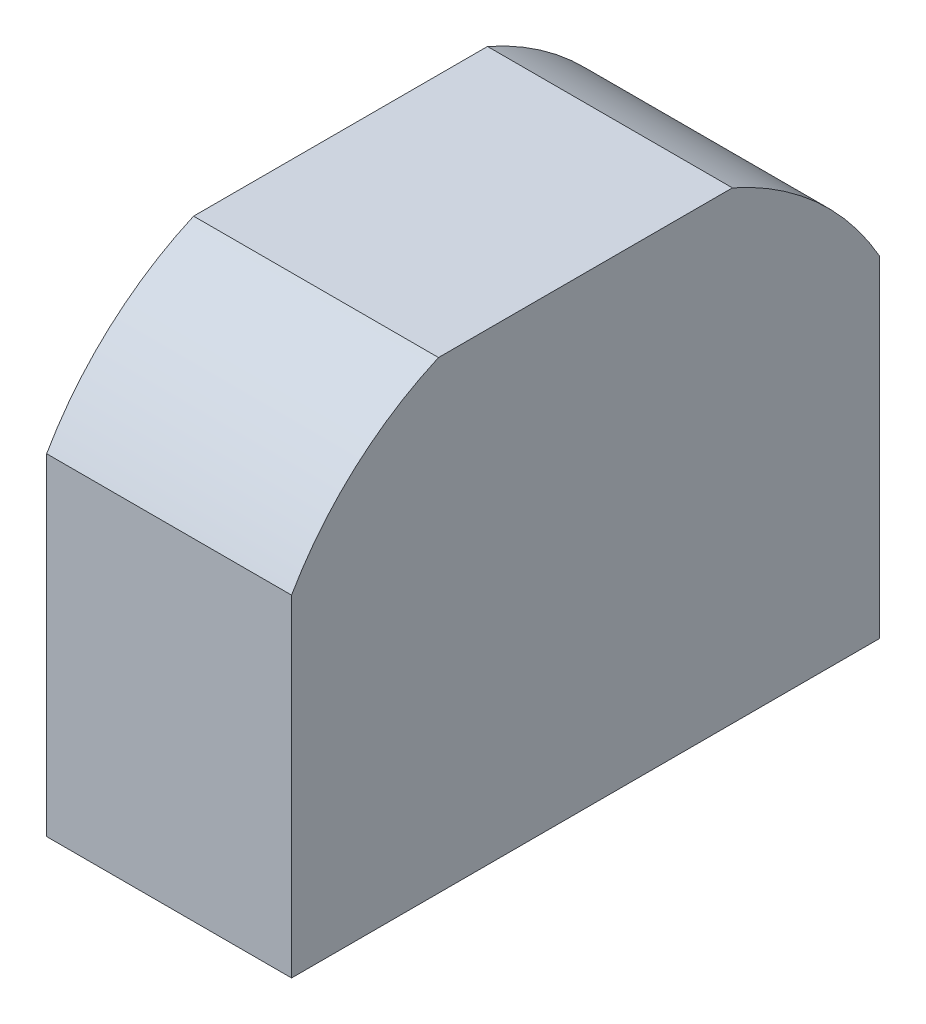
SolidWorks part; units mm, degrees
ref_plane "Front Plane" through (0, 0, 0) normal (0, 0, 1) x (1, 0, 0)
ref_plane "Top Plane" through (0, 0, 0) normal (0, 1, 0) x (1, 0, 0)
ref_plane "Right Plane" through (0, 0, 0) normal (1, 0, 0) x (0, 0, -1)
sketch "Sketch1" plane through (0, 0, 0) normal (0, 0, 1) x (1, 0, 0)
  line L0 (-77.5, 0) -> (77.5, 0)
  arc A0 (77.5, 0) -> (-77.5, 0) centre (0, 0) ccw
  dimension "D1" = 155
extrude "Boss-Extrude1" add sketch "Sketch1" along normal blind 15 and the other way blind 15
sketch "Sketch2" plane through (0, 0, 0) normal (0, -1, 0) x (1, 0, 0)
  line L0 (77.5, -15) -> (77.5, 15) construction
  line L2 (-77.5, 15) -> (77.5, 15) construction
  line L3 (-77.5, -15) -> (77.5, -15) construction
  line L4 (0, 0) -> (0, -15) construction
  circle A0 centre (67.5, 10) radius 2.45
  circle A1 centre (67.5, -10) radius 2.45
  circle A2 centre (-67.5, -10) radius 2.45
  circle A3 centre (-67.5, 10) radius 2.45
  dimension "D1" = 4.9
  dimension "D2" = 10
  dimension "D3" = 2
  dimension "D4" = 20
  dimension "D5" = 5
extrude "Boss-Extrude2" add sketch "Sketch2" along normal blind 5
sketch "Sketch3" plane through (0, 0, 15) normal (0, 0, 1) x (1, 0, 0)
  line L0 (-77.5, 0) -> (77.5, 0) construction
  line L1 (-53.9096, 20) -> (53.9096, 20)
  arc A0 (-53.9096, 20) -> (53.9096, 20) centre (0, 0) ccw
  arc A1 (77.5, 0) -> (-77.5, 0) centre (0, 0) ccw construction
  dimension "D1" = 20
  dimension "D2" = 20
extrude "Cut-Extrude1" cut sketch "Sketch3" against normal through all
ref_plane "Plane1" through (-77.5, 0, 0) normal (1, 0, 0) x (0, 0, -1)
sketch "Sketch4" plane through (-77.5, 0, 0) normal (1, 0, 0) x (0, 0, -1)
  line L0 (0, 0) -> (0, 50)
  line L1 (-30, 0) -> (30, 0)
  line L2 (30, 0) -> (30, 33.8467)
  line L3 (-30, 0) -> (-30, 33.8467)
  arc A0 (30, 33.8467) -> (0, 50) centre (2.0603, 17.8917) ccw
  arc A1 (-30, 33.8467) -> (0, 50) centre (-2.0603, 17.8917) cw
  dimension "D1" = 30
  dimension "D2" = 50
extrude "Boss-Extrude3" add sketch "Sketch4" along normal blind 25 contours L2 A0 L0 L1 | A1 L3 L1 L0 region at (-77.5, 23.0652, 14.1925) region at (-77.5, 23.0652, -14.1925)
sketch "Sketch5" plane through (-77.5, 0, 0) normal (-1, 0, 0) x (0, 0, 1)
  line L0 (0, 50) -> (0, 0) construction
  line L1 (-30, 0) -> (30, 0) construction
  line L2 (6.0867, 27.5001) -> (19.3685, 32.2732)
  line L3 (19.3685, 32.2732) -> (19.3685, 20.2366)
  line L4 (19.3685, 20.2366) -> (6.0867, 20.2366)
  line L5 (6.0867, 20.2366) -> (6.0867, 27.5001)
  line L6 (-12.8314, 8.3557) -> (-12.8314, 6.2286)
  line L7 (-2.6625, 11.728) -> (2.6625, 11.728)
  line L8 (0, 11.728) -> (0, 6.2286)
  line L9 (-2.6625, 6.2286) -> (2.6625, 6.2286)
  line L10 (2.6625, 11.728) -> (2.6625, 6.2286)
  line L11 (6.0867, 11.728) -> (9.459, 11.728)
  line L12 (6.0867, 11.728) -> (6.0867, 6.2286)
  line L13 (6.0867, 6.2286) -> (12.8314, 6.2286)
  line L14 (12.8314, 8.3557) -> (12.8314, 6.2286)
  line L15 (-6.0867, 6.2286) -> (-12.8314, 6.2286)
  line L16 (-6.0867, 11.728) -> (-6.0867, 6.2286)
  line L17 (-6.0867, 11.728) -> (-9.459, 11.728)
  line L18 (-2.6625, 11.728) -> (-2.6625, 6.2286)
  line L19 (-6.0867, 20.2366) -> (-6.0867, 27.5001)
  line L20 (-19.3685, 20.2366) -> (-6.0867, 20.2366)
  line L21 (-19.3685, 32.2732) -> (-19.3685, 20.2366)
  line L22 (-6.0867, 27.5001) -> (-19.3685, 32.2732)
  arc A0 (9.459, 11.728) -> (12.8314, 6.2286) centre (8.3955, 7.2921) cw
  arc A1 (-9.459, 11.728) -> (-12.8314, 6.2286) centre (-8.3955, 7.2921) ccw
extrude "Cut-Extrude2" cut sketch "Sketch5" against normal blind 3 contours L19 L22 L21 L20 | L5 L4 L3 L2 | A0 L11 L12 L13 L14 | L10 L7 L8 L9 | L7 L18 L9 L8 | L17 A1 L6 L15 L16 region at (-77.5, 25.16, 13.275) region at (-77.5, 8.7843, -9.1999) region at (-77.5, 8.9783, -1.3313) region at (-77.5, 8.9783, 1.3313) region at (-77.5, 8.7843, 9.1999) region at (-77.5, 25.16, -13.275)
sketch "Sketch6" plane through (0, 0, 15) normal (0, 0, 1) x (1, 0, 0)
  line L1 (83.3238, -12.5068) -> (-52.5, -12.5068)
  line L2 (83.3238, -12.5068) -> (83.3238, 47.3493)
  line L3 (83.3238, 47.3493) -> (-52.5, 47.3493)
  line L4 (-52.5, -12.5068) -> (-52.5, 47.3493)
extrude "Cut-Extrude3" cut sketch "Sketch6" against normal through all
sketch "Sketch7" plane through (-77.5, 0, 0) normal (1, 0, 0) x (0, 0, -1)
  line L1 (-15, 77.5) -> (15, 77.5)
  line L2 (-15, 77.5) -> (-15, 47.3493)
  line L3 (-15, 47.3493) -> (15, 47.3493)
  line L4 (15, 77.5) -> (15, 47.3493)
extrude "Cut-Extrude6" cut sketch "Sketch7" along normal through all
